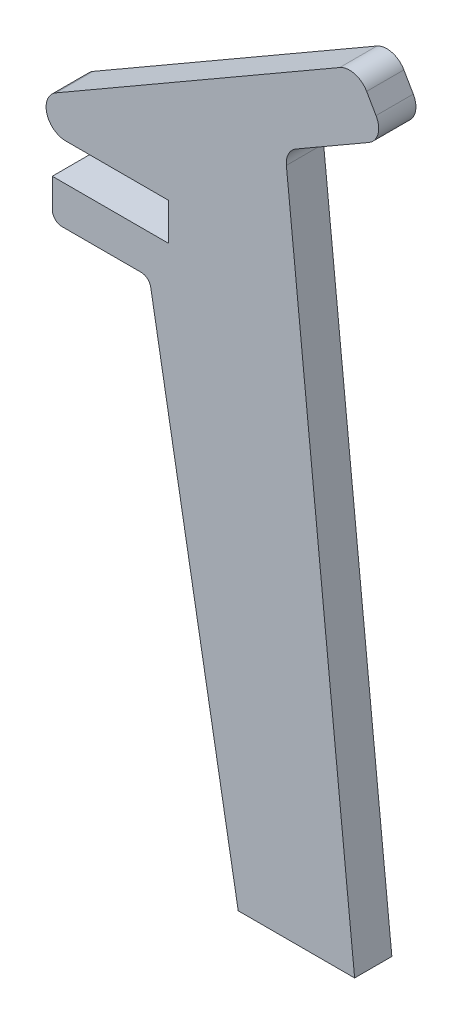
SolidWorks part; units mm, degrees
ref_plane "Front Plane" through (0, 0, 0) normal (0, 0, 1) x (1, 0, 0)
ref_plane "Top Plane" through (0, 0, 0) normal (0, 1, 0) x (1, 0, 0)
ref_plane "Right Plane" through (0, 0, 0) normal (1, 0, 0) x (0, 0, -1)
sketch "Sketch1" plane through (0, 0, 0) normal (0, 0, 1) x (1, 0, 0)
  line L0 (159.9956, -83.8859) -> (150.4706, -67.3882) construction
  line L1 (127, -102.9359) -> (159.9956, -83.8859) construction
  line L2 (150.4706, -67.3882) -> (31.146, -136.2802) construction
  line L3 (-88.9, -136.2802) -> (88.9, -136.2802) construction
  line L4 (88.9, -136.2802) -> (88.9, -148.4722) construction
  line L5 (-88.9, -148.4722) -> (88.9, -148.4722) construction
  line L6 (111.6616, -326.2722) -> (149.7616, -326.2722) construction
  line L8 (149.7616, -326.2722) -> (127, -102.9359) construction
  line L9 (159.9956, -83.8859) -> (150.4706, -67.3882)
  line L10 (127, -102.9359) -> (159.9956, -83.8859)
  line L11 (150.4706, -67.3882) -> (31.146, -136.2802)
  line L12 (31.146, -136.2802) -> (88.9, -136.2802)
  line L13 (88.9, -136.2802) -> (88.9, -148.4722)
  line L14 (50.8, -148.4722) -> (88.9, -148.4722)
  line L15 (111.6616, -326.2722) -> (149.7616, -326.2722)
  line L17 (149.7616, -326.2722) -> (127, -102.9359)
  line L18 (82.55, -161.1722) -> (111.6616, -326.2722) construction
  line L19 (50.8, -161.1722) -> (50.8, -148.4722) construction
  line L20 (82.55, -161.1722) -> (50.8, -161.1722) construction
  line L21 (82.55, -161.1722) -> (111.6616, -326.2722)
  line L22 (50.8, -161.1722) -> (50.8, -148.4722)
  line L23 (82.55, -161.1722) -> (50.8, -161.1722)
extrude "Boss-Extrude1" add sketch "Sketch1" along normal mid plane 12.192
fillet "Fillet1" radius 6.45 4 edges at (31.146, -136.2802, 0) (127, -102.9359, 0) (150.4706, -67.3882, 0) (159.9956, -83.8859, 0)
fillet "Fillet2" radius 3.175 2 edges at (82.55, -161.1722, 0) (50.8, -161.1722, 0)
